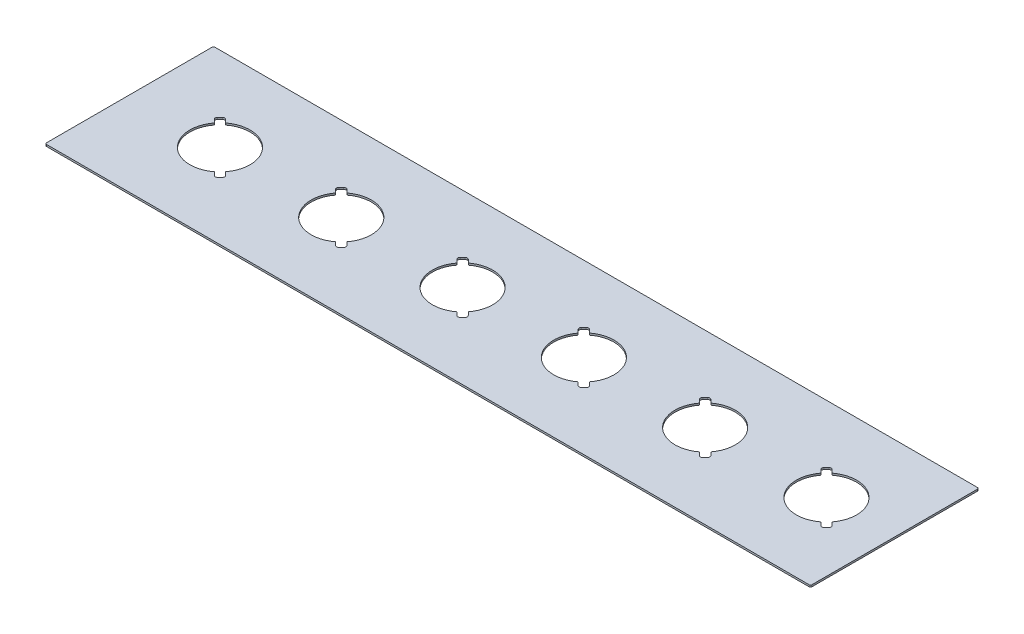
SolidWorks part; units mm, degrees
material "E-Glass Fiber"
ref_plane "Front" through (0, 0, 0) normal (0, 0, 1) x (1, 0, 0)
ref_plane "Top" through (0, 0, 0) normal (0, 1, 0) x (1, 0, 0)
ref_plane "Right" through (0, 0, 0) normal (1, 0, 0) x (0, 0, -1)
sketch "Sketch2" plane through (0, 0, 0) normal (0, 1, 0) x (1, 0, 0)
  line L1 (-317.5, 69.85) -> (317.5, 69.85)
  line L2 (-317.5, 69.85) -> (-317.5, -69.85)
  line L3 (-317.5, -69.85) -> (317.5, -69.85)
  line L5 (317.5, 69.85) -> (317.5, -69.85)
  line L6 (-317.5, 69.85) -> (317.5, -69.85) construction
  line L13 (180.1482, -15.1494) -> (182.7999, -17.8011) construction
  line L14 (182.7999, -20.6295) -> (180.8907, -22.5387) construction
  line L18 (178.0623, -22.5387) -> (175.4106, -19.887) construction
  line L19 (142.4601, 22.5387) -> (145.1118, 19.887) construction
  line L20 (140.3742, 15.1494) -> (137.7225, 17.8011) construction
  line L24 (137.7225, 20.6295) -> (139.6317, 22.5387) construction
  line L25 (180.1482, -15.1494) -> (182.7999, -17.8011)
  line L30 (182.7999, -20.6295) -> (180.8907, -22.5387)
  line L31 (178.0623, -22.5387) -> (175.4106, -19.887)
  line L32 (142.4601, 22.5387) -> (145.1118, 19.887)
  line L36 (140.3742, 15.1494) -> (137.7225, 17.8011)
  line L37 (137.7225, 20.6295) -> (139.6317, 22.5387)
  line L38 (39.7394, 15.1494) -> (37.0877, 17.8011) construction
  line L42 (243.0949, 22.5387) -> (245.7466, 19.887) construction
  line L43 (238.3573, 20.6295) -> (240.2665, 22.5387) construction
  line L44 (241.009, 15.1494) -> (238.3573, 17.8011) construction
  line L45 (243.0949, 22.5387) -> (245.7466, 19.887)
  line L46 (238.3573, 20.6295) -> (240.2665, 22.5387)
  line L47 (241.009, 15.1494) -> (238.3573, 17.8011)
  line L48 (280.783, -15.1494) -> (283.4347, -17.8011) construction
  line L49 (283.4347, -20.6295) -> (281.5255, -22.5387) construction
  line L50 (278.6971, -22.5387) -> (276.0454, -19.887) construction
  line L51 (280.783, -15.1494) -> (283.4347, -17.8011)
  line L52 (283.4347, -20.6295) -> (281.5255, -22.5387)
  line L53 (278.6971, -22.5387) -> (276.0454, -19.887)
  line L78 (37.0877, 20.6295) -> (38.9969, 22.5387) construction
  line L79 (41.8253, 22.5387) -> (44.477, 19.887) construction
  line L80 (79.5134, -15.1494) -> (82.1651, -17.8011) construction
  line L81 (82.1651, -20.6295) -> (80.2559, -22.5387) construction
  line L82 (77.4275, -22.5387) -> (74.7758, -19.887) construction
  line L83 (39.7394, 15.1494) -> (37.0877, 17.8011)
  line L84 (37.0877, 20.6295) -> (38.9969, 22.5387)
  line L85 (41.8253, 22.5387) -> (44.477, 19.887)
  line L86 (79.5134, -15.1494) -> (82.1651, -17.8011)
  line L87 (82.1651, -20.6295) -> (80.2559, -22.5387)
  line L88 (77.4275, -22.5387) -> (74.7758, -19.887)
  line L89 (-60.8954, 15.1494) -> (-63.5471, 17.8011) construction
  line L90 (-63.5471, 20.6295) -> (-61.6379, 22.5387) construction
  line L91 (-58.8095, 22.5387) -> (-56.1578, 19.887) construction
  line L92 (-21.1214, -15.1494) -> (-18.4697, -17.8011) construction
  line L93 (-18.4697, -20.6295) -> (-20.3789, -22.5387) construction
  line L94 (-23.2073, -22.5387) -> (-25.859, -19.887) construction
  line L95 (-60.8954, 15.1494) -> (-63.5471, 17.8011)
  line L96 (-63.5471, 20.6295) -> (-61.6379, 22.5387)
  line L97 (-58.8095, 22.5387) -> (-56.1578, 19.887)
  line L98 (-21.1214, -15.1494) -> (-18.4697, -17.8011)
  line L99 (-18.4697, -20.6295) -> (-20.3789, -22.5387)
  line L100 (-23.2073, -22.5387) -> (-25.859, -19.887)
  line L101 (-161.5302, 15.1494) -> (-164.1819, 17.8011) construction
  line L102 (-164.1819, 20.6295) -> (-162.2727, 22.5387) construction
  line L103 (-159.4443, 22.5387) -> (-156.7926, 19.887) construction
  line L104 (-121.7562, -15.1494) -> (-119.1045, -17.8011) construction
  line L105 (-119.1045, -20.6295) -> (-121.0137, -22.5387) construction
  line L106 (-123.8421, -22.5387) -> (-126.4938, -19.887) construction
  line L107 (-161.5302, 15.1494) -> (-164.1819, 17.8011)
  line L108 (-164.1819, 20.6295) -> (-162.2727, 22.5387)
  line L109 (-159.4443, 22.5387) -> (-156.7926, 19.887)
  line L110 (-121.7562, -15.1494) -> (-119.1045, -17.8011)
  line L111 (-119.1045, -20.6295) -> (-121.0137, -22.5387)
  line L112 (-123.8421, -22.5387) -> (-126.4938, -19.887)
  line L113 (-222.391, -15.1494) -> (-219.7393, -17.8011) construction
  line L114 (-219.7393, -20.6295) -> (-221.6485, -22.5387) construction
  line L115 (-224.4769, -22.5387) -> (-227.1286, -19.887) construction
  line L116 (-260.0791, 22.5387) -> (-257.4274, 19.887) construction
  line L117 (-264.8167, 20.6295) -> (-262.9075, 22.5387) construction
  line L118 (-262.165, 15.1494) -> (-264.8167, 17.8011) construction
  line L119 (-222.391, -15.1494) -> (-219.7393, -17.8011)
  line L120 (-219.7393, -20.6295) -> (-221.6485, -22.5387)
  line L121 (-224.4769, -22.5387) -> (-227.1286, -19.887)
  line L122 (-260.0791, 22.5387) -> (-257.4274, 19.887)
  line L123 (-264.8167, 20.6295) -> (-262.9075, 22.5387)
  line L124 (-262.165, 15.1494) -> (-264.8167, 17.8011)
  arc A16 (182.7999, -20.6295) -> (182.7999, -17.8011) centre (181.3857, -19.2153) ccw construction
  arc A20 (178.0623, -22.5387) -> (180.8907, -22.5387) centre (179.4765, -21.1245) ccw construction
  arc A24 (142.4601, 22.5387) -> (139.6317, 22.5387) centre (141.0459, 21.1245) ccw construction
  arc A28 (137.7225, 20.6295) -> (137.7225, 17.8011) centre (139.1367, 19.2153) ccw construction
  arc A45 (182.7999, -20.6295) -> (182.7999, -17.8011) centre (181.3857, -19.2153) ccw
  arc A46 (178.0623, -22.5387) -> (180.8907, -22.5387) centre (179.4765, -21.1245) ccw
  arc A47 (241.009, 15.1494) -> (276.0454, -19.887) centre (260.896, 0) ccw
  arc A48 (243.0949, 22.5387) -> (240.2665, 22.5387) centre (241.6807, 21.1245) ccw construction
  arc A49 (238.3573, 20.6295) -> (238.3573, 17.8011) centre (239.7715, 19.2153) ccw construction
  arc A50 (243.0949, 22.5387) -> (240.2665, 22.5387) centre (241.6807, 21.1245) ccw
  arc A51 (238.3573, 20.6295) -> (238.3573, 17.8011) centre (239.7715, 19.2153) ccw
  arc A52 (283.4347, -20.6295) -> (283.4347, -17.8011) centre (282.0205, -19.2153) ccw construction
  arc A53 (278.6971, -22.5387) -> (281.5255, -22.5387) centre (280.1113, -21.1245) ccw construction
  arc A54 (283.4347, -20.6295) -> (283.4347, -17.8011) centre (282.0205, -19.2153) ccw
  arc A55 (278.6971, -22.5387) -> (281.5255, -22.5387) centre (280.1113, -21.1245) ccw
  arc A56 (280.783, -15.1494) -> (245.7466, 19.887) centre (260.896, 0) ccw
  arc A79 (142.4601, 22.5387) -> (139.6317, 22.5387) centre (141.0459, 21.1245) ccw
  arc A80 (137.7225, 20.6295) -> (137.7225, 17.8011) centre (139.1367, 19.2153) ccw
  arc A81 (180.1482, -15.1494) -> (145.1118, 19.887) centre (160.2612, 0) ccw
  arc A82 (140.3742, 15.1494) -> (175.4106, -19.887) centre (160.2612, 0) ccw
  arc A83 (37.0877, 20.6295) -> (37.0877, 17.8011) centre (38.5019, 19.2153) ccw construction
  arc A84 (41.8253, 22.5387) -> (38.9969, 22.5387) centre (40.4111, 21.1245) ccw construction
  arc A85 (82.1651, -20.6295) -> (82.1651, -17.8011) centre (80.7509, -19.2153) ccw construction
  arc A86 (77.4275, -22.5387) -> (80.2559, -22.5387) centre (78.8417, -21.1245) ccw construction
  arc A87 (37.0877, 20.6295) -> (37.0877, 17.8011) centre (38.5019, 19.2153) ccw
  arc A88 (41.8253, 22.5387) -> (38.9969, 22.5387) centre (40.4111, 21.1245) ccw
  arc A89 (82.1651, -20.6295) -> (82.1651, -17.8011) centre (80.7509, -19.2153) ccw
  arc A90 (77.4275, -22.5387) -> (80.2559, -22.5387) centre (78.8417, -21.1245) ccw
  arc A91 (-63.5471, 20.6295) -> (-63.5471, 17.8011) centre (-62.1329, 19.2153) ccw construction
  arc A92 (-58.8095, 22.5387) -> (-61.6379, 22.5387) centre (-60.2237, 21.1245) ccw construction
  arc A93 (-18.4697, -20.6295) -> (-18.4697, -17.8011) centre (-19.8839, -19.2153) ccw construction
  arc A94 (-23.2073, -22.5387) -> (-20.3789, -22.5387) centre (-21.7931, -21.1245) ccw construction
  arc A95 (-63.5471, 20.6295) -> (-63.5471, 17.8011) centre (-62.1329, 19.2153) ccw
  arc A96 (-58.8095, 22.5387) -> (-61.6379, 22.5387) centre (-60.2237, 21.1245) ccw
  arc A97 (-18.4697, -20.6295) -> (-18.4697, -17.8011) centre (-19.8839, -19.2153) ccw
  arc A98 (-23.2073, -22.5387) -> (-20.3789, -22.5387) centre (-21.7931, -21.1245) ccw
  arc A99 (-164.1819, 20.6295) -> (-164.1819, 17.8011) centre (-162.7677, 19.2153) ccw construction
  arc A100 (-159.4443, 22.5387) -> (-162.2727, 22.5387) centre (-160.8585, 21.1245) ccw construction
  arc A101 (-119.1045, -20.6295) -> (-119.1045, -17.8011) centre (-120.5187, -19.2153) ccw construction
  arc A102 (-123.8421, -22.5387) -> (-121.0137, -22.5387) centre (-122.4279, -21.1245) ccw construction
  arc A103 (-164.1819, 20.6295) -> (-164.1819, 17.8011) centre (-162.7677, 19.2153) ccw
  arc A104 (-159.4443, 22.5387) -> (-162.2727, 22.5387) centre (-160.8585, 21.1245) ccw
  arc A105 (-119.1045, -20.6295) -> (-119.1045, -17.8011) centre (-120.5187, -19.2153) ccw
  arc A106 (-123.8421, -22.5387) -> (-121.0137, -22.5387) centre (-122.4279, -21.1245) ccw
  arc A107 (-219.7393, -20.6295) -> (-219.7393, -17.8011) centre (-221.1535, -19.2153) ccw construction
  arc A108 (-224.4769, -22.5387) -> (-221.6485, -22.5387) centre (-223.0627, -21.1245) ccw construction
  arc A109 (-260.0791, 22.5387) -> (-262.9075, 22.5387) centre (-261.4933, 21.1245) ccw construction
  arc A110 (-264.8167, 20.6295) -> (-264.8167, 17.8011) centre (-263.4025, 19.2153) ccw construction
  arc A111 (-219.7393, -20.6295) -> (-219.7393, -17.8011) centre (-221.1535, -19.2153) ccw
  arc A112 (-224.4769, -22.5387) -> (-221.6485, -22.5387) centre (-223.0627, -21.1245) ccw
  arc A113 (-260.0791, 22.5387) -> (-262.9075, 22.5387) centre (-261.4933, 21.1245) ccw
  arc A114 (-264.8167, 20.6295) -> (-264.8167, 17.8011) centre (-263.4025, 19.2153) ccw
  arc A115 (79.5134, -15.1494) -> (44.477, 19.887) centre (59.6264, 0) ccw
  arc A116 (-21.1214, -15.1494) -> (-56.1578, 19.887) centre (-41.0084, 0) ccw
  arc A117 (-121.7562, -15.1494) -> (-156.7926, 19.887) centre (-141.6432, 0) ccw
  arc A118 (-222.391, -15.1494) -> (-257.4274, 19.887) centre (-242.278, 0) ccw
  arc A119 (-262.165, 15.1494) -> (-227.1286, -19.887) centre (-242.278, 0) ccw
  arc A120 (-161.5302, 15.1494) -> (-126.4938, -19.887) centre (-141.6432, 0) ccw
  arc A121 (-60.8954, 15.1494) -> (-25.859, -19.887) centre (-41.0084, 0) ccw
  arc A122 (39.7394, 15.1494) -> (74.7758, -19.887) centre (59.6264, 0) ccw
  point P0 (0, 0)
  dimension "D1" = 635
  dimension "D2" = 139.7
extrude "Boss-Extrude1" add sketch "Sketch2" along normal blind 1.524
sketch "Sketch3" [suppressed] plane through (0, 1.524, 0) normal (0, 1, 0) x (1, 0, 0)
  line L42 (-317.5, -69.85) -> (-292.1, -69.85) construction
  line L43 (285.896, 0) -> (287.166, 0)
  line L44 (-317.5, 69.85) -> (-317.5, -69.85) construction
  line L45 (-317.5, 49.8475) -> (-317.5, 69.85) construction
  line L46 (260.896, -26.27) -> (260.896, 26.27) construction
  line L47 (-292.1, -69.85) -> (-292.1, 69.85)
  line L48 (-292.1, 49.8475) -> (-317.5, 49.8475)
  line L49 (234.626, 26.27) -> (287.166, 26.27) construction
  line L50 (-292.1, -49.8475) -> (-317.5, -49.8475)
  line L51 (-317.5, -49.8475) -> (-317.5, -69.85) construction
  line L52 (287.166, 0) -> (287.166, -26.27)
  line L53 (287.166, 0) -> (234.626, 0) construction
  line L54 (234.626, -26.27) -> (234.626, 26.27) construction
  line L55 (260.896, 26.27) -> (234.626, 26.27)
  line L57 (234.626, 26.27) -> (234.626, 0)
  line L58 (234.626, 0) -> (235.896, 0)
  line L59 (260.896, 26.27) -> (260.896, 25)
  line L61 (287.166, -26.27) -> (260.896, -26.27)
  line L63 (260.896, -26.27) -> (260.896, -25)
  line L64 (160.261, -26.27) -> (160.261, 26.27) construction
  line L65 (133.991, 26.27) -> (186.531, 26.27) construction
  line L67 (186.531, -26.27) -> (133.991, -26.27) construction
  line L68 (186.531, 0) -> (133.991, 0) construction
  line L69 (133.991, -26.27) -> (133.991, 26.27) construction
  line L70 (160.261, 26.27) -> (133.991, 26.27)
  line L71 (133.991, 26.27) -> (133.991, 0)
  line L72 (133.991, 0) -> (135.261, 0)
  line L73 (160.261, 26.27) -> (160.261, 25)
  line L74 (185.261, 0) -> (186.531, 0)
  line L75 (186.531, 0) -> (186.531, -26.27)
  line L76 (186.531, -26.27) -> (160.261, -26.27)
  line L77 (160.261, -26.27) -> (160.261, -25)
  line L78 (59.626, -26.27) -> (59.626, 26.27) construction
  line L79 (33.356, 26.27) -> (85.896, 26.27) construction
  line L81 (85.896, -26.27) -> (33.356, -26.27) construction
  line L82 (85.896, 0) -> (33.356, 0) construction
  line L83 (33.356, -26.27) -> (33.356, 26.27) construction
  line L85 (59.626, 25) -> (59.626, 26.27)
  line L86 (59.626, 26.27) -> (33.356, 26.27)
  line L87 (33.356, 26.27) -> (33.356, 0)
  line L88 (33.356, 0) -> (34.626, 0)
  line L90 (84.626, 0) -> (85.896, 0)
  line L92 (85.896, 0) -> (85.896, -26.27)
  line L93 (85.896, -26.27) -> (59.626, -26.27)
  line L94 (59.626, -26.27) -> (59.626, -25)
  line L96 (-292.1, 49.5863) -> (-292.1, 88.9) construction
  line L97 (317.5, 69.85) -> (-317.5, 69.85) construction
  line L98 (-317.5, -69.85) -> (317.5, -69.85) construction
  line L99 (317.5, 69.85) -> (-317.5, 69.85) construction
  arc A24 (241.009, 15.1494) -> (276.0454, -19.887) centre (260.896, 0) ccw construction
  arc A25 (280.783, -15.1494) -> (245.7466, 19.887) centre (260.896, 0) ccw construction
  arc A26 (140.374, 15.1494) -> (175.4104, -19.887) centre (160.261, 0) ccw construction
  arc A27 (180.148, -15.1494) -> (145.1116, 19.887) centre (160.261, 0) ccw construction
  point P8 (260.896, 0)
  point P16 (160.261, 0)
  point P17 (260.896, 0)
  point P37 (160.261, 0)
  point P52 (59.626, 0)
  point P60 (59.626, 0)
  dimension "D1" = 20.0025
fillet "Fillet1" radius 1.27 4 edges at (317.5, 0.762, -69.85) (317.5, 0.762, 69.85) (-317.5, 0.762, 69.85) (-317.5, 0.762, -69.85)
